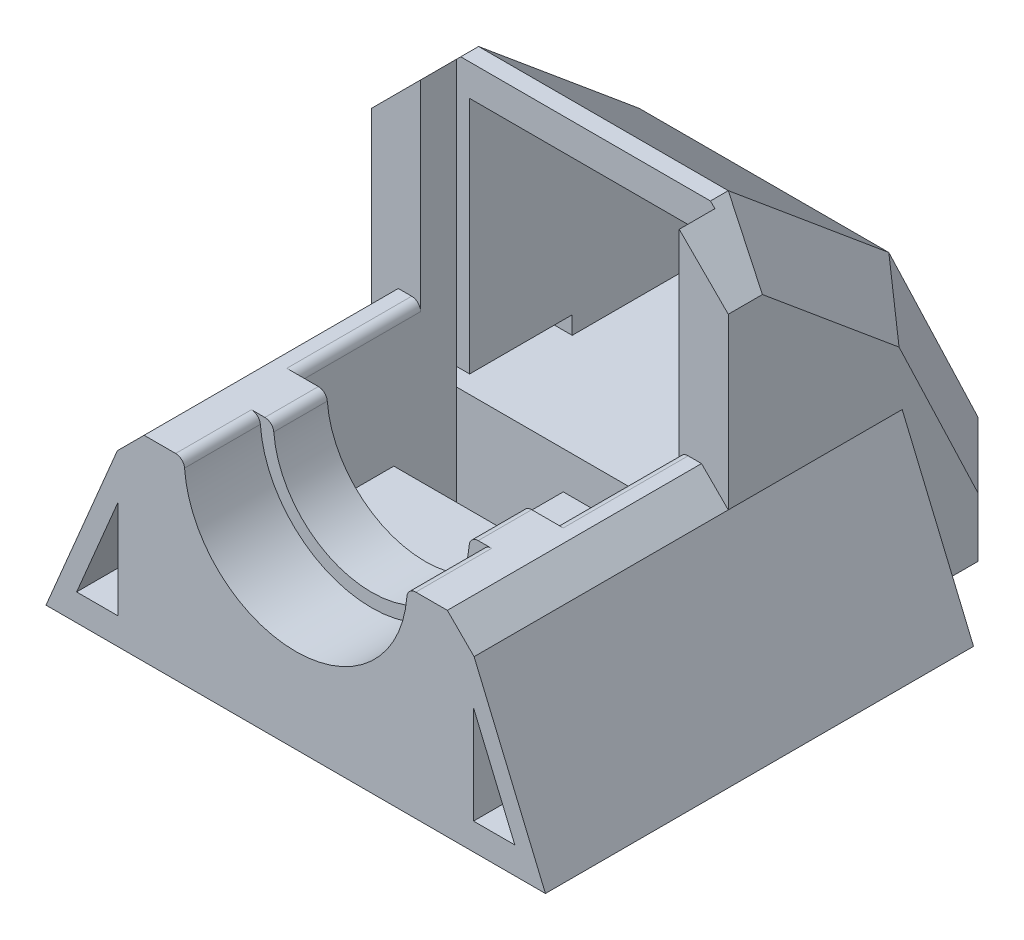
SolidWorks part; units mm, degrees
ref_plane "Ebene vorne" through (0, 0, 0) normal (0, 0, 1) x (1, 0, 0)
ref_plane "Ebene oben" through (0, 0, 0) normal (0, 1, 0) x (1, 0, 0)
ref_plane "Ebene rechts" through (0, 0, 0) normal (1, 0, 0) x (0, 0, -1)
sketch "Skizze1" plane through (0, 0, 0) normal (0, 0, 1) x (1, 0, 0)
  line L1 (0, 0) -> (20, 0)
  line L2 (0, 0) -> (0, 22)
  line L3 (0, 22) -> (20, 22)
  line L4 (20, 0) -> (20, 22)
  dimension "D1" = 22
  dimension "D2" = 20
extrude "Aufsatz-Linear austragen1" add sketch "Skizze1" along normal blind 35
sketch "Skizze2" plane through (0, 0, 35) normal (0, 0, 1) x (1, 0, 0)
  line L0 (0, 22) -> (0, 0) construction
  line L1 (20, 22) -> (0, 22) construction
  circle A0 centre (10, 11) radius 5.5
  dimension "D3" = 11
  dimension "D1" = 10
  dimension "D2" = 11
extrude "Schnitt-Linear austragen1" cut sketch "Skizze2" against normal blind 11
sketch "Skizze3" plane through (0, 0, 35) normal (0, 0, 1) x (1, 0, 0)
  line L0 (20, 0) -> (20, 22) construction
  line L1 (20, 22) -> (0, 22) construction
  circle A0 centre (10, 11) radius 6.25
  dimension "D1" = 10
  dimension "D2" = 11
extrude "Schnitt-Linear austragen2" cut sketch "Skizze3" against normal blind 8
sketch "Skizze5" plane through (0, 0, 24) normal (0, 0, 1) x (1, 0, 0)
  line L0 (0, 22) -> (0, 0) construction
  line L1 (2.75, 3.75) -> (17.25, 3.75)
  line L2 (2.75, 3.75) -> (2.75, 22)
  line L3 (2.75, 22) -> (17.25, 22)
  line L4 (17.25, 3.75) -> (17.25, 22)
  line L6 (0, 0) -> (20, 0) construction
  dimension "D1" = 18.25
  dimension "D2" = 14.5
  dimension "D3" = 2.75
  dimension "D4" = 3.75
extrude "Schnitt-Linear austragen3" cut sketch "Skizze5" against normal blind 9
sketch "Skizze13" plane through (0, 0, 35) normal (0, 0, 1) x (1, 0, 0)
  line L0 (20, 0) -> (20, 22) construction
  line L1 (0, 22) -> (20, 22)
  line L2 (0, 22) -> (0, 11)
  line L3 (0, 11) -> (20, 11)
  line L4 (20, 22) -> (20, 11)
extrude "Schnitt-Linear austragen6" cut sketch "Skizze13" against normal blind 18
sketch "Skizze16" plane through (0, 0, 0) normal (-1, 0, 0) x (0, 0, 1)
  line L0 (14, 22) -> (5, 14.5)
  line L1 (17, 22) -> (0, 22) construction
  line L2 (5, 14.5) -> (0, 4)
  line L3 (0, 22) -> (0, 0) construction
  line L4 (0, 4) -> (0, 22)
  line L5 (0, 22) -> (14, 22)
  line L6 (17, 22) -> (17, 11) construction
  dimension "D1" = 3
  dimension "D2" = 5
  dimension "D3" = 18
  dimension "D4" = 10.5
extrude "Schnitt-Linear austragen7" cut sketch "Skizze16" against normal through all
fillet "Verrundung1" radius 0.5 6 edges at (16.25, 11, 31) (3.75, 11, 31) (4.5, 11, 25.5) (15.5, 11, 25.5) (17.25, 11, 20.5) (2.75, 11, 20.5)
chamfer "Fase1" distance 3 angle 45 2 edges at (20, 22, 15.5) (0, 22, 15.5)
chamfer "Fase2" distance 3 angle 45 2 edges at (0, 16.75, 7.7) (20, 16.75, 7.7)
chamfer "Fase3" distance 3 angle 45 4 edges at (20, 6.0129, 0.9585) (20, 2, 0) (0, 6.0129, 0.9585) (0, 2, 0)
chamfer "Fase4" distance 1.5 angle 45 2 edges at (20, 11, 26) (0, 11, 26)
sketch "Skizze17" plane through (0, 3.75, 0) normal (0, 1, 0) x (1, 0, 0)
  line L1 (2.75, -15) -> (8.75, -15)
  line L2 (2.75, -15) -> (2.75, -18.5)
  line L3 (2.75, -18.5) -> (8.75, -18.5)
  line L4 (8.75, -15) -> (8.75, -18.5)
  dimension "D1" = 6
  dimension "D2" = 3.5
extrude "Schnitt-Linear austragen8" cut sketch "Skizze17" against normal through all
sketch "Skizze18" plane through (0, 0, 0) normal (-1, 0, 0) x (0, 0, 1)
  line L0 (17, 11) -> (35, 11) construction
  line L1 (35, 0) -> (31.25, 0)
  line L2 (35, 0) -> (35, 11)
  line L3 (35, 11) -> (31.25, 11)
  line L4 (31.25, 0) -> (31.25, 11)
  dimension "D1" = 3.75
extrude "Schnitt-Linear austragen9" cut sketch "Skizze18" against normal up to surface (20 mm away) up to face at (20, 9.1173, 16.564)
ref_plane "Ebene1" through (10, 0, 0) normal (-1, 0, 0) x (0, 0, 1)
sketch "Skizze22" plane through (10, 0, 0) normal (-1, 0, 0) x (0, 0, 1)
  line L0 (15, 20.2299) -> (6.6172, 13.2443)
  line L1 (15, 3.75) -> (15, 21.75) construction
  line L2 (7.4258, 12.6164) -> (5, 14.5) construction
  line L3 (6.6172, 13.2443) -> (5.76, 11.8961)
  line L4 (5.76, 11.8961) -> (3.76, 11.8961)
  line L5 (5, 14.5) -> (0, 4) construction
  line L6 (3.76, 11.8961) -> (0.8806, 5.8493)
  line L7 (0.8806, 5.8493) -> (6.0352, 5.8493)
  line L8 (6.0352, 5.8493) -> (15, 5.8493)
  line L9 (15, 5.8493) -> (15, 20.2299)
  line L10 (14, 22) -> (5, 14.5) construction
  dimension "D1" = 2
  dimension "D2" = 2
extrude "Schnitt-Linear austragen10" cut sketch "Skizze22" against normal blind 6.5 and the other way blind 6.5
sketch "Skizze23" plane through (0, 0, 31.25) normal (0, 0, 1) x (1, 0, 0)
  line L0 (0, 9.5) -> (-4, 0)
  line L1 (-4, 0) -> (0, 0)
  line L2 (0, 0) -> (0, 9.5)
  dimension "D1" = 4
extrude "Aufsatz-Linear austragen2" add sketch "Skizze23" against normal blind 24
mirror "Spiegeln1" about plane through (10, 0, 0) normal (-1, 0, 0) of "Aufsatz-Linear austragen2"
sketch "Skizze24" plane through (0, 0, 31.25) normal (0, 0, 1) x (1, 0, 0)
  line L0 (0.0324, 1.5) -> (-2.2834, 1.5)
  line L1 (-2.2834, 1.5) -> (0.0324, 7)
  line L2 (0.0324, 7) -> (0.0324, 1.5)
  line L3 (0, 9.5) -> (-4, 0) construction
  line L4 (24, 0) -> (-4, 0) construction
  dimension "D1" = 1
  dimension "D2" = 1.5
  dimension "D3" = 5.5
extrude "Schnitt-Linear austragen11" cut sketch "Skizze24" against normal blind 22
sketch "Skizze26" plane through (16.5, 0, 0) normal (-1, 0, 0) x (0, 0, 1)
  line L1 (15, 5.8493) -> (9.25, 5.8493)
  line L2 (15, 5.8493) -> (15, 6.8493)
  line L3 (15, 6.8493) -> (9.25, 6.8493)
  line L4 (9.25, 5.8493) -> (9.25, 6.8493)
  dimension "D1" = 5.75
  dimension "D2" = 1
extrude "Schnitt-Linear austragen12" cut sketch "Skizze26" against normal blind 4
mirror "Spiegeln2" about plane through (10, 0, 0) normal (-1, 0, 0) of "Schnitt-Linear austragen12"
mirror "Spiegeln3" about plane through (10, 0, 0) normal (-1, 0, 0) of "Schnitt-Linear austragen11"
